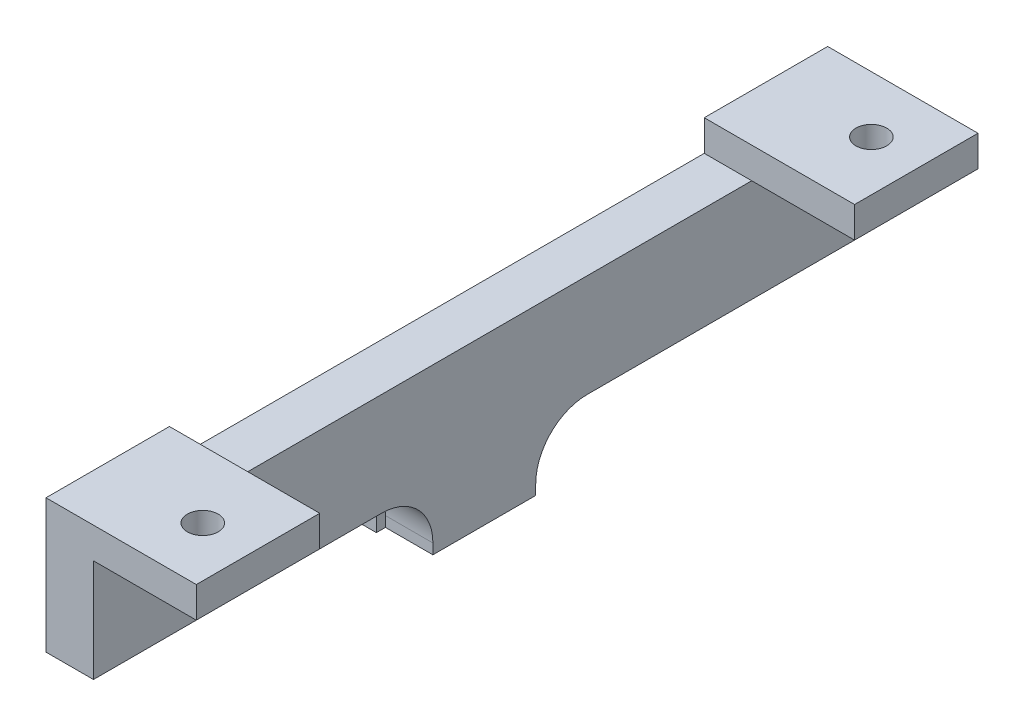
SolidWorks part; units mm, degrees
ref_plane "Front Plane" through (0, 0, 0) normal (0, 0, 1) x (1, 0, 0)
ref_plane "Top Plane" through (0, 0, 0) normal (0, 1, 0) x (1, 0, 0)
ref_plane "Right Plane" through (0, 0, 0) normal (1, 0, 0) x (0, 0, -1)
sketch "Sketch1" plane through (0, 0, 0) normal (0, 1, 0) x (1, 0, 0)
  line L0 (0, 8.5) -> (0, -8.5) construction
  line L1 (-3, -11.3279) -> (3, -11.3279)
  line L2 (-3, -11.3279) -> (-3, 11.3279)
  line L3 (-3, 11.3279) -> (3, 11.3279)
  line L4 (3, -11.3279) -> (3, -5)
  line L5 (-3, -11.3279) -> (3, 11.3279) construction
  line L6 (-3, 11.3279) -> (3, -11.3279) construction
  line L7 (3, -5) -> (7.6154, -5)
  line L8 (7.6154, -5) -> (7.6154, 5)
  line L9 (7.6154, 5) -> (3, 5)
  line L10 (3, 5) -> (3, 11.3279)
  circle A0 centre (0, 8.5) radius 1.5
  circle A1 centre (0, -8.5) radius 1.5
  point P0 (0, 0)
  point P10 (0, 0)
  point P13 (7.6154, 0)
  point P16 (-3, 0)
  dimension "D1" = 3
  dimension "D2" = 17
  dimension "D3" = 6
  dimension "D4" = 10
extrude "Boss-Extrude1" add sketch "Sketch1" along normal blind 3
sketch "Sketch3" plane through (0, 3, 0) normal (0, 1, 0) x (1, 0, 0)
  line L0 (7.6154, 5) -> (3, 5) construction
  line L1 (7.6154, 5) -> (3, 5)
  line L2 (7.6154, 5) -> (7.6154, -5)
  line L3 (7.6154, -5) -> (3, -5)
  line L4 (3, 5) -> (3, -5)
  line L5 (7.6154, -5) -> (7.6154, 5) construction
  line L6 (3, -5) -> (7.6154, -5) construction
extrude "Boss-Extrude2" add sketch "Sketch3" along normal blind 12.9998
fillet "Fillet7" radius 1 2 edges at (3, 1.5, -11.3279) (3, 1.5, 11.3279)
sketch "Sketch7" plane through (0, 0, 0) normal (0, -1, 0) x (1, 0, 0)
  line L0 (-3.6553, -6.3921) -> (-3.7819, 6.4785)
  arc A0 (-3.6553, -6.3921) -> (-3.7819, 6.4785) centre (-8.1114, 0) ccw
extrude "Cut-Extrude4" cut sketch "Sketch7" against normal blind 10
fillet "Fillet8" radius 4 1 edges at (3, 3, 0)
sketch "Sketch8" plane through (7.6154, 0, 0) normal (1, 0, 0) x (0, 0, -1)
  line L0 (-5, 15.9998) -> (5, 15.9998) construction
  line L1 (-38, 5.9998) -> (38, 5.9998)
  line L2 (-38, 5.9998) -> (-38, 15.9998)
  line L3 (-38, 15.9998) -> (38, 15.9998)
  line L4 (38, 5.9998) -> (38, 15.9998)
  line L7 (-5, 0) -> (5, 0) construction
  point P0 (0, 10.9824)
  point P9 (0, 0)
  point P10 (0, 5.9998)
  dimension "D1" = 10
  dimension "D2" = 76
extrude "Boss-Extrude3" add sketch "Sketch8" against normal up to surface (4.6154 mm away) up to face at (3, 9.9902, -0.0004)
sketch "Sketch9" plane through (0, 15.9998, 0) normal (0, 1, 0) x (1, 0, 0)
  line L0 (7.6154, -38) -> (7.6154, 38) construction
  line L1 (3, 38) -> (17.6154, 38)
  line L2 (3, 38) -> (3, 26)
  line L3 (3, 26) -> (17.6154, 26)
  line L4 (17.6154, 38) -> (17.6154, 26)
  line L5 (3, -38) -> (17.6154, -38)
  line L6 (3, -38) -> (3, -26)
  line L7 (3, -26) -> (17.6154, -26)
  line L8 (17.6154, -38) -> (17.6154, -26)
  line L9 (12.7451, 32.5) -> (12.7451, -32.5) construction
  circle A0 centre (12.7451, 32.5) radius 1.5
  circle A1 centre (12.7451, -32.5) radius 1.5
  point P16 (7.6154, 0)
  point P17 (12.7451, 0)
  dimension "D2" = 3
  dimension "D1" = 10
  dimension "D3" = 65
  dimension "D4" = 12
extrude "Boss-Extrude4" add sketch "Sketch9" along normal blind 3
fillet "Fillet9" radius 5 1 edges at (5.3077, 5.9998, 5)
fillet "Fillet10" radius 5 1 edges at (5.3077, 5.9998, -5)
sketch "Sketch10" plane through (0, 3, 0) normal (0, 1, 0) x (1, 0, 0)
  line L0 (3.5564, 5.88) -> (3.5564, -5.88) construction
  line L1 (3.5564, 15.865) -> (-6.2169, 15.865)
  line L2 (3.5564, 15.865) -> (3.5564, 5.88)
  line L3 (3.5564, 5.88) -> (-6.2169, 5.88)
  line L4 (-6.2169, 15.865) -> (-6.2169, 5.88)
  line L5 (-9.1574, -13.6403) -> (3.5564, -13.6403)
  line L6 (-9.1574, -13.6403) -> (-9.1574, -5.88)
  line L7 (-9.1574, -5.88) -> (3.5564, -5.88)
  line L8 (3.5564, -13.6403) -> (3.5564, -5.88)
  line L9 (7.6154, -26) -> (7.6154, 26) construction
  point P10 (7.6154, 0)
  point P11 (3.5564, 0)
  dimension "D1" = 11.76
extrude "Cut-Extrude6" cut sketch "Sketch10" against normal blind 10
